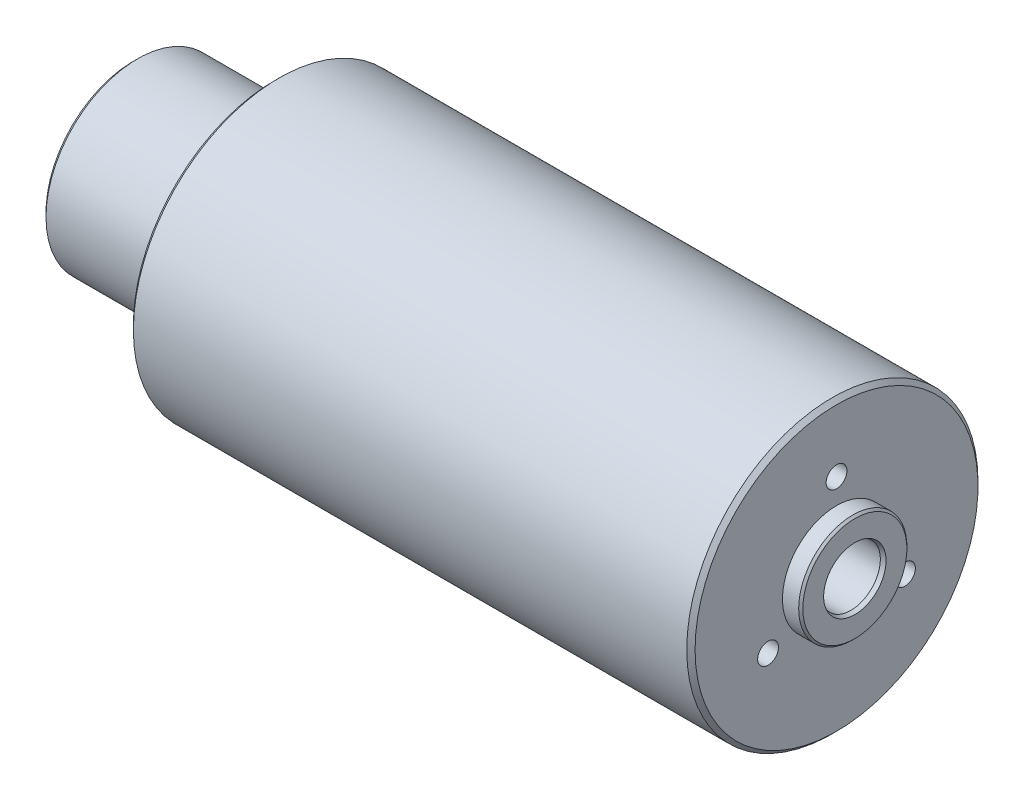
SolidWorks part; units mm, degrees
ref_plane "Face" through (0, 0, 0) normal (0, 0, 1) x (1, 0, 0)
ref_plane "Dessus" through (0, 0, 0) normal (0, 1, 0) x (1, 0, 0)
ref_plane "Droite" through (0, 0, 0) normal (1, 0, 0) x (0, 0, -1)
sketch "Esquisse1" plane through (0, 0, 0) normal (0, 0, 1) x (1, 0, 0)
  line L0 (-71.1252, 0) -> (22.9527, 0) construction
  line L1 (2.2, 0) -> (2.2, 6.5)
  line L2 (2.2, 6.5) -> (0, 6.5)
  line L3 (0, 6.5) -> (0, 17.5)
  line L4 (0, 17.5) -> (-67.5007, 17.5)
  line L5 (-67.5007, 17.5) -> (-67.5007, 11)
  line L6 (2.2, 0) -> (-84.5007, 0)
  line L7 (-67.5007, 11) -> (-84.5007, 11)
  line L8 (-84.5007, 11) -> (-84.5007, 0)
  dimension "D1" = 17.5
  dimension "D2" = 6.5
  dimension "D3" = 67.5007
  dimension "D4" = 2.2
  dimension "D5" = 17
  dimension "D6" = 11
revolve "Base-Révolution" add sketch "Esquisse1" angle 360 about L0
chamfer "Chanfrein2" distance 0.25 angle 45 1 edges at (2.2, 0, 6.5)
hole_wizard "Trou taraudé M2.5x0.451" positions "Esquisse3" profile "Esquisse2" tap size "M2.5x0.45" standard "ISO"
sketch "Esquisse3" plane through (0, 0, 0) normal (1, 0, 0) x (0, 0, -1)
  line L0 (0, 0) -> (0, 13.9918) construction
  point P0 (0, 9.5)
  dimension "D1" = 9.5
sketch "Esquisse2" plane through (0, 9.5, 0) normal (0, 1, 0) x (0, 0, -1)
  line L0 (0, 0) -> (0, 7.3659)
  line L1 (0, 7.3659) -> (1.025, 6.75)
  line L2 (1.025, 6.75) -> (1.025, 4.5)
  line L3 (1.025, 4.5) -> (1.25, 4.5)
  line L4 (1.25, 4.5) -> (1.25, 0)
  line L5 (1.25, 0) -> (0, 0)
  line L10 (0, 7.3659) -> (-1.025, 6.75) construction
  line L11 (0, -6.35) -> (0, 107.95) construction
  dimension "Diamètre du trou pour taraudage" = 2.05
  dimension "Profondeur du trou pour taraudage" = 6.75
  dimension "Diamètre du filetage" = 2.5
  dimension "Profondeur du filetage" = 4.5
  dimension "Angle de pointe" = 118
ref_axis "Axe1" through (-21.1252, 0, 0) along (-1, 0, 0)
pattern_circular "Répétition circulaire1" count 3 every 120 about axis through (-21.1252, 0, 0) along (-1, 0, 0) of "Trou taraudé M2.5x0.451"
chamfer "Chanfrein3" distance 0.5 angle 45 3 edges at (-84.5007, 0, 11) (-67.5007, 0, 17.5) (0, 0, 17.5)
hole_wizard "Dégagement pour M6.51" positions "Esquisse5" profile "Esquisse4" hole size "M6.5" standard "ISO"
sketch "Esquisse5" plane through (2.2, 0, 0) normal (1, 0, 0) x (0, 0, -1)
  point P0 (0, 0)
sketch "Esquisse4" plane through (2.2, 0, 0) normal (0, 1, 0) x (0, 0, -1)
  line L0 (0, 0) -> (0, 22.1331)
  line L1 (0, 22.1331) -> (3.55, 20)
  line L2 (3.55, 20) -> (3.55, 0.4828)
  line L3 (3.55, 0.4828) -> (3.75, 0)
  line L5 (3.75, 0) -> (0, 0)
  line L6 (-3.55, 0.4828) -> (-3.75, 0) construction
  line L10 (0, 22.1331) -> (-3.55, 20) construction
  line L11 (0, -6.35) -> (0, 107.95) construction
  dimension "Diamètre du perçage" = 7.1
  dimension "Profondeur du perçage" = 20
  dimension "Diamètre du fraisage entrant" = 7.5
  dimension "Angle du fraisage entrant" = 45
  dimension "Angle de pointe" = 118
